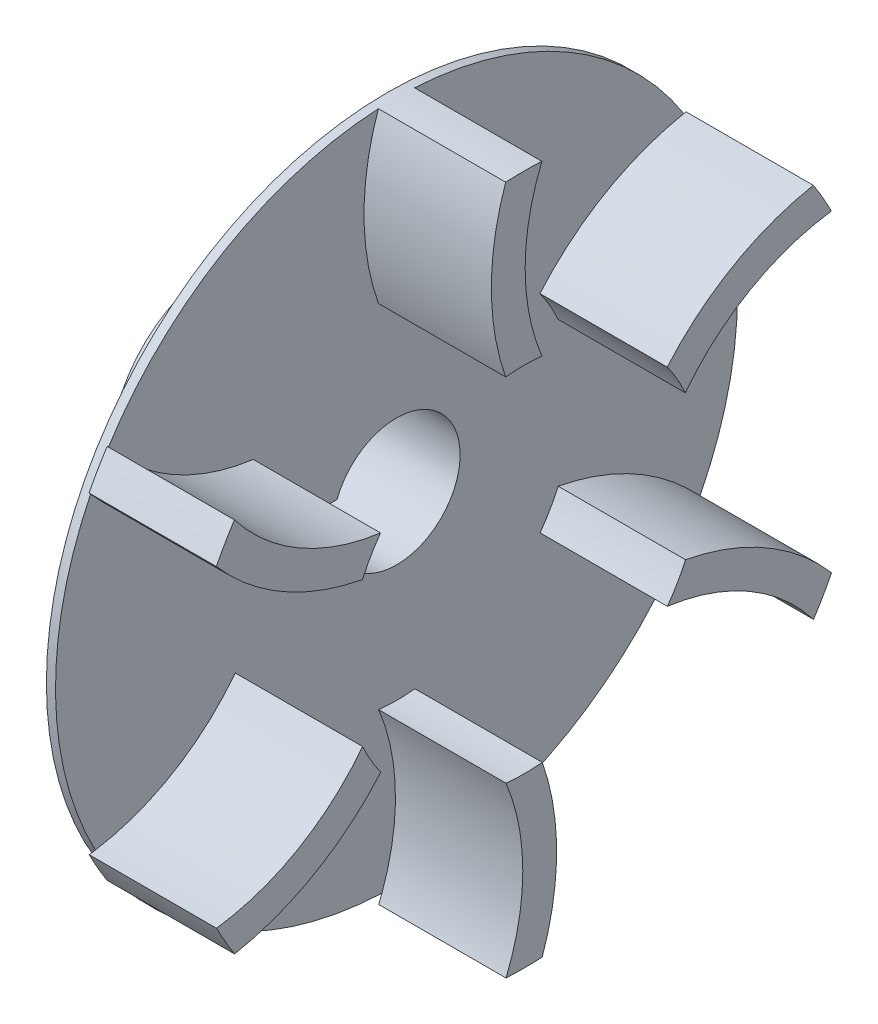
SolidWorks part; units mm, degrees
note: The reader was unsure of these and kept them because the rebuilt part matched: shared geometry of "Sketch4<2>".
ref_plane "Front Plane" through (0, 0, 0) normal (1, 0, 0) x (0, 1, 0)
ref_plane "Top Plane" through (0, 0, 0) normal (0, 0, 1) x (0, 1, 0)
ref_plane "Right Plane" through (0, 0, 0) normal (0, 1, 0) x (-1, 0, 0)
sketch "Sketch3" plane through (0, 0, 0) normal (1, 0, 0) x (0, 1, 0)
  circle A0 centre (0, 0) radius 37.5
  dimension "D1" = 75
extrude "Boss-Extrude1" add sketch "Sketch3" against normal blind 1
sketch "Sketch4" plane through (-1, 0, 0) normal (-1, 0, 0) x (0, -1, 0)
  line L0 (-2.5, 8.5383) -> (2.5, 8.5383)
  line L1 (2.5, 8.5383) -> (2.5, 6.5383)
  line L2 (-2.5, 8.5383) -> (-2.5, 6.5383)
  circle A0 centre (0, 0) radius 12.5
  arc A1 (-2.5, 6.5383) -> (2.5, 6.5383) centre (0, 0) ccw
  point P6 (0, 8.5383)
  dimension "D1" = 25
  dimension "D2" = 14
  dimension "D3" = 5
  dimension "D4" = 2
extrude "Boss-Extrude2" add sketch "Sketch4" along normal blind 18
fillet "Fillet1" radius 6 1 edges at (-1, 0, -12.5)
sketch "Sketch7" plane through (0, 0, 0) normal (1, 0, 0) x (0, 1, 0)
  circle A0 centre (0, 0) radius 19 construction
  circle A1 centre (0, 0) radius 37.5
  arc A2 (18.8955, 1.9903) -> (37.4471, 1.9903) centre (28.1713, -24.4286) cw
  arc A3 (18.8955, -1.9903) -> (37.4471, -1.9903) centre (28.1713, -24.4286) cw
  arc A4 (18.8955, 1.9903) -> (18.8955, -1.9903) centre (0, 0) cw
  arc A5 (37.4471, 1.9903) -> (37.4471, -1.9903) centre (0, 0) cw
  point P10 (0, 0)
  point P12 (0, 0)
  dimension "D1" = 38
  dimension "D2" = 75
  dimension "D3" = 3.72
  dimension "D4" = 28
extrude "Boss-Extrude4" add sketch "Sketch7" along normal blind 14 contours A2 A4 A3 A1
pattern_circular "CirPattern1" count 6 over 360 about axis through (0, -0.4572, -0.0185) along (1, 0, 0) of "Boss-Extrude4"
extrude "Cut-Extrude1" cut sketch "Sketch4<2>" against normal blind 14 contours L2 A1 L1 L0
sketch "Sketch4<2>" plane through (-1, 0, 0) normal (-1, 0, 0) x (0, -1, 0) same geometry as "Sketch4"
